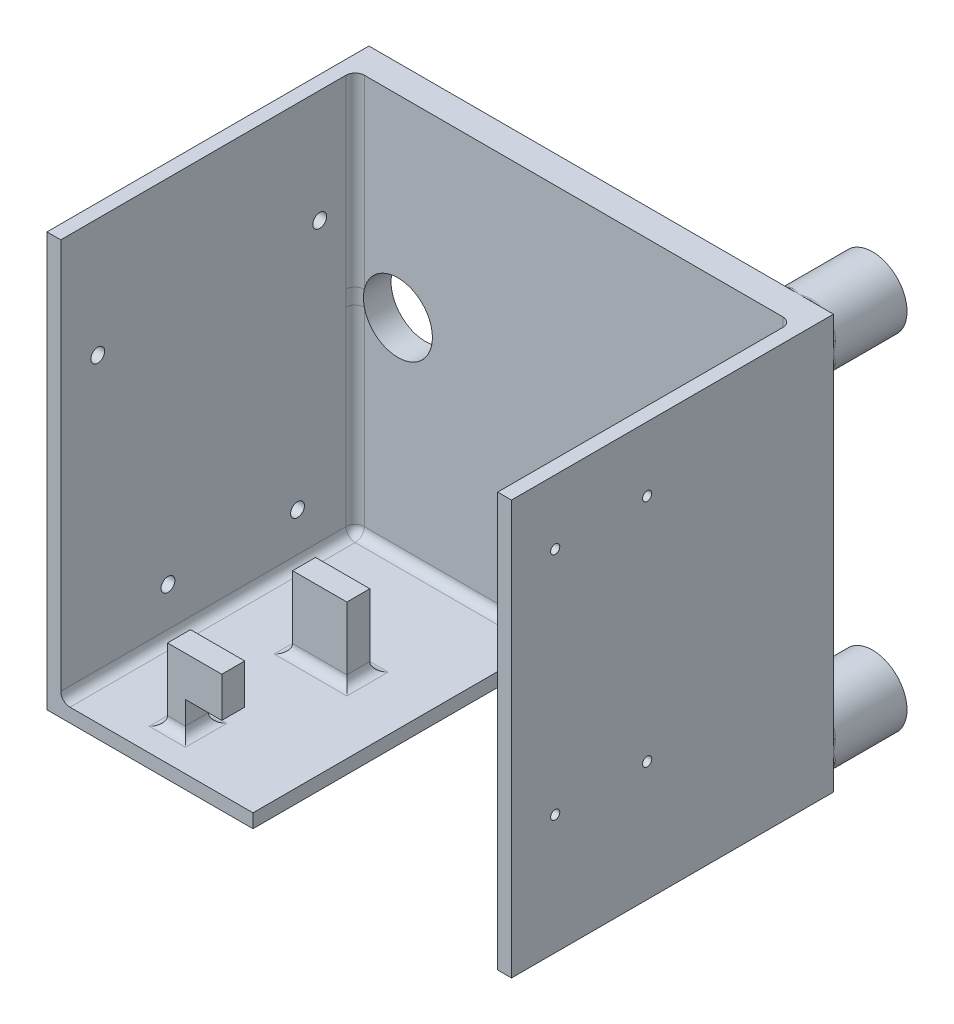
SolidWorks part; units mm, degrees
ref_plane "Front Plane" through (0, 0, 0) normal (0, 0, 1) x (1, 0, 0)
ref_plane "Top Plane" through (0, 0, 0) normal (0, 1, 0) x (1, 0, 0)
ref_plane "Right Plane" through (0, 0, 0) normal (1, 0, 0) x (0, 0, -1)
sketch "Sketch1" plane through (0, 0, 0) normal (0, 0, 1) x (1, 0, 0)
  line L0 (50.5, 48) -> (-50.5, 48)
  line L1 (47.5, -45) -> (-47.5, -45)
  line L2 (47.5, -45) -> (47.5, 45)
  line L3 (47.5, 45) -> (-47.5, 45)
  line L4 (-47.5, -45) -> (-47.5, 45)
  line L5 (47.5, -45) -> (-47.5, 45) construction
  line L6 (47.5, 45) -> (-47.5, -45) construction
  line L7 (-50.5, -48) -> (-50.5, 48)
  line L8 (50.5, -48) -> (-50.5, -48)
  line L9 (50.5, -48) -> (50.5, 48)
  point P0 (0, 0)
  dimension "D1" = 90
  dimension "D2" = 95
  dimension "D3" = 3
extrude "Boss-Extrude1" add sketch "Sketch1" along normal blind 70
sketch "Sketch3" plane through (50.5, 0, 0) normal (1, 0, 0) x (0, 0, -1)
  line L0 (-70, -48) -> (0, -48) construction
  line L1 (0, 48) -> (-6, 48)
  line L2 (0, 48) -> (0, -48)
  line L3 (0, -48) -> (-6, -48)
  line L4 (-6, 48) -> (-6, -48)
  dimension "D1" = 6
extrude "Boss-Extrude3" add sketch "Sketch3" against normal blind 102
sketch "Sketch5" plane through (-50.5, 0, 0) normal (-1, 0, 0) x (0, 0, 1)
  line L0 (70, 48) -> (6, 48) construction
  line L1 (11.16, 31.5) -> (64.5, 31.5)
  line L2 (11.16, 31.5) -> (11.16, -37.08)
  line L3 (11.16, -37.08) -> (64.5, -37.08)
  line L4 (64.5, 31.5) -> (64.5, -37.08)
  line L5 (70, 48) -> (70, -48) construction
  circle A0 centre (61.96, 16.27) radius 1.5
  circle A1 centre (13.7, 17.5) radius 1.5
  point P4 (37.83, 31.5)
  point P9 (64.5, 16.27)
  point P10 (61.96, 16.27)
  point P11 (13.7, 17.5)
  dimension "D8" = 14
  dimension "D1" = 68.58
  dimension "D2" = 53.34
  dimension "D3" = 16.5
  dimension "D4" = 5.5
  dimension "D5" = 15.23
  dimension "D6" = 2.54
  dimension "D7" = 2.54
sketch "Sketch6" plane through (-50.5, 0, 0) normal (-1, 0, 0) x (0, 0, 1)
  line L0 (11.16, -37.08) -> (64.5, -37.08) construction
  line L1 (11.16, 31.5) -> (11.16, -37.08) construction
  circle A0 centre (18.52, -34.54) radius 1.5
  circle A1 centre (46.69, -34.54) radius 1.5
  point P0 (18.52, -34.08)
  point P1 (-61.2014, -14.8235)
  point P2 (-50.5223, 20.308)
  point P3 (39.33, -37.08)
  point P5 (18.52, -34.54)
  point P8 (46.69, -34.54)
  dimension "D1" = 7.36
  dimension "D2" = 28.17
  dimension "D3" = 2.54
  dimension "D4" = 2.54
extrude "Cut-Extrude1" cut sketch "Sketch6" against normal blind 10
extrude "Cut-Extrude2" cut sketch "Sketch5" against normal blind 10 contours A0
extrude "Cut-Extrude3" cut sketch "Sketch5<3>" against normal blind 10 contours A1
sketch "Sketch5<3>" plane through (-50.5, 0, 0) normal (-1, 0, 0) x (0, 0, 1) same geometry as "Sketch5"
sketch "Sketch7" plane through (0, -48, 0) normal (0, -1, 0) x (1, 0, 0)
  line L0 (50.5, 70) -> (50.5, 0) construction
  line L1 (-19.5, 58) -> (-31.3, 58)
  line L2 (-19.5, 58) -> (-19.5, 35.8)
  line L3 (-19.5, 35.8) -> (-31.3, 35.8)
  line L4 (-31.3, 58) -> (-31.3, 35.8)
  line L5 (-50.5, 70) -> (50.5, 70) construction
  line L7 (-31.3, 35.8) -> (-19.5, 35.8)
  line L8 (-31.3, 35.8) -> (-31.3, 30.8)
  line L9 (-31.3, 30.8) -> (-19.5, 30.8)
  line L10 (-19.5, 35.8) -> (-19.5, 30.8)
  line L11 (-31.3, 58) -> (-19.5, 58)
  line L12 (-31.3, 58) -> (-31.3, 63)
  line L13 (-31.3, 63) -> (-19.5, 63)
  line L14 (-19.5, 58) -> (-19.5, 63)
  dimension "D1" = 11.8
  dimension "D2" = 22.2
  dimension "D3" = 70
  dimension "D4" = 12
  dimension "D5" = 5
  dimension "D6" = 5
sketch "Sketch18" plane through (50.5, 0, 0) normal (1, 0, 0) x (0, 0, -1)
  line L0 (0, -48) -> (0, 48) construction
  line L1 (-70, 48) -> (0, 48)
  line L2 (-70, 48) -> (-70, 42)
  line L3 (-70, 42) -> (0, 42)
  line L4 (0, 48) -> (0, 42)
  dimension "D1" = 6
extrude "Cut-Extrude12" cut sketch "Sketch18" against normal through all
extrude "Boss-Extrude5" add sketch "Sketch7" against normal blind 18.7 contours L10 L3 L8 L9 | L12 L11 L14 L13 region at (-25.4, -48, 33.3)
sketch "Sketch19" plane through (50.5, 0, 0) normal (1, 0, 0) x (0, 0, -1)
  line L0 (-70, -48) -> (0, -48) construction
  line L1 (-65.5, 33) -> (-35.5, 33)
  line L2 (-65.5, 33) -> (-65.5, -27)
  line L3 (-65.5, -27) -> (-35.5, -27)
  line L4 (-35.5, 33) -> (-35.5, -27)
  line L5 (-70, -48) -> (-70, 42) construction
  line L6 (-50.5, 33) -> (-50.5, -36.939) construction
  line L7 (-65.5, 3) -> (-29.056, 3) construction
  circle A0 centre (-60.5, -22) radius 1
  circle A1 centre (-60.5, 28) radius 1
  circle A2 centre (-40.5, -22) radius 1
  circle A3 centre (-40.5, 28) radius 1
  dimension "D7" = 2
  dimension "D1" = 21
  dimension "D2" = 30
  dimension "D3" = 60
  dimension "D4" = 4.5
  dimension "D5" = 5
  dimension "D6" = 5
extrude "Cut-Extrude13" cut sketch "Sketch19" against normal blind 22 contours A2 | A0 | A1 | A3
sketch "Sketch20" plane through (0, 0, 70) normal (0, 0, 1) x (1, 0, 0)
  line L0 (-50.5, -48) -> (50.5, -48) construction
  line L1 (47.5, -45) -> (-5.7108, -45)
  line L2 (47.5, -45) -> (47.5, -48)
  line L3 (47.5, -48) -> (-5.7108, -48)
  line L4 (-5.7108, -45) -> (-5.7108, -48)
extrude "Cut-Extrude15" cut sketch "Sketch20" against normal blind 64
sketch "Sketch21" plane through (0, 0, 0) normal (0, 0, -1) x (-1, 0, 0)
  line L0 (51.5, 42) -> (-50.5, 42) construction
  line L1 (-50.5, -48) -> (-50.5, 42) construction
  circle A0 centre (-43, 34.5) radius 7.5
  dimension "D1" = 15
sketch "Sketch23" plane through (0, 0, 0) normal (0, 0, -1) x (-1, 0, 0)
  line L0 (-50.5, -48) -> (-50.5, 42) construction
  line L1 (51.5, -48) -> (-50.5, -48) construction
  circle A0 centre (-43, -40.5) radius 7.5
extrude "Boss-Extrude6" add sketch "Sketch23" along normal blind 16
extrude "Boss-Extrude7" add sketch "Sketch21" along normal blind 16
sketch "Sketch24" plane through (0, 0, 63) normal (0, 0, 1) x (1, 0, 0)
  line L0 (-19.5, -45) -> (-31.3, -45) construction
  line L1 (-27.4, -38) -> (-20.4, -38)
  line L2 (-27.4, -38) -> (-27.4, -45)
  line L3 (-27.4, -45) -> (-20.4, -45)
  line L4 (-20.4, -38) -> (-20.4, -45)
  line L7 (-31.3, -29.3) -> (-31.3, -45) construction
  dimension "D1" = 7
  dimension "D2" = 7
  dimension "D3" = 3.9
extrude "Cut-Extrude16" cut sketch "Sketch24" against normal blind 9.5
sketch "Sketch25" plane through (0, 0, 6) normal (0, 0, 1) x (1, 0, 0)
  circle A0 centre (-38.1935, 0) radius 7.5
  dimension "D1" = 15
extrude "Cut-Extrude17" cut sketch "Sketch25" against normal blind 10
fillet "Fillet1" radius 2 1 edges at (-47.5, -45, 38)
fillet "Fillet2" radius 2 3 edges at (-25.6054, -45, 6) (-46.9142, -44.4142, 6) (-47.5, -0.5, 6)
sketch "Sketch26" plane through (0, -48, 0) normal (0, -1, 0) x (1, 0, 0)
  line L1 (-50.5, 6) -> (-51.5, 6)
  line L2 (-50.5, 6) -> (-50.5, 0)
  line L3 (-50.5, 0) -> (-51.5, 0)
  line L4 (-51.5, 6) -> (-51.5, 0)
extrude "Cut-Extrude18" cut sketch "Sketch26" against normal through all
sketch "Sketch27" plane through (0, 0, 63) normal (0, 0, 1) x (1, 0, 0)
sketch "Sketch28" plane through (0, 0, 63) normal (0, 0, 1) x (1, 0, 0)
  line L1 (-20.4, -38) -> (-19.5, -38)
  line L2 (-20.4, -38) -> (-20.4, -45)
  line L3 (-20.4, -45) -> (-19.5, -45)
  line L4 (-19.5, -38) -> (-19.5, -45)
extrude "Cut-Extrude19" cut sketch "Sketch28" against normal up to next
fillet "Fillet3" radius 2 1 edges at (-25.4, -45, 35.8)
fillet "Fillet4" radius 2 1 edges at (-25.4, -45, 30.8)
fillet "Fillet5" radius 2 1 edges at (-19.5, -45, 33.3)
fillet "Fillet6" radius 2 7 edges at (47.5, -3, 6) (-5.7108, -45.5, 6) (-31.3, -45, 60.5) (-29.35, -45, 63) (-27.4, -45, 60.5) (-29.35, -45, 58) (-31.3, -45, 33.3)
fillet "Fillet7" radius 1 4 edges at (48.3033, -45.8033, 0) (37.6967, -35.1967, 0) (48.3033, 39.8033, 0) (37.6967, 29.1967, 0)
